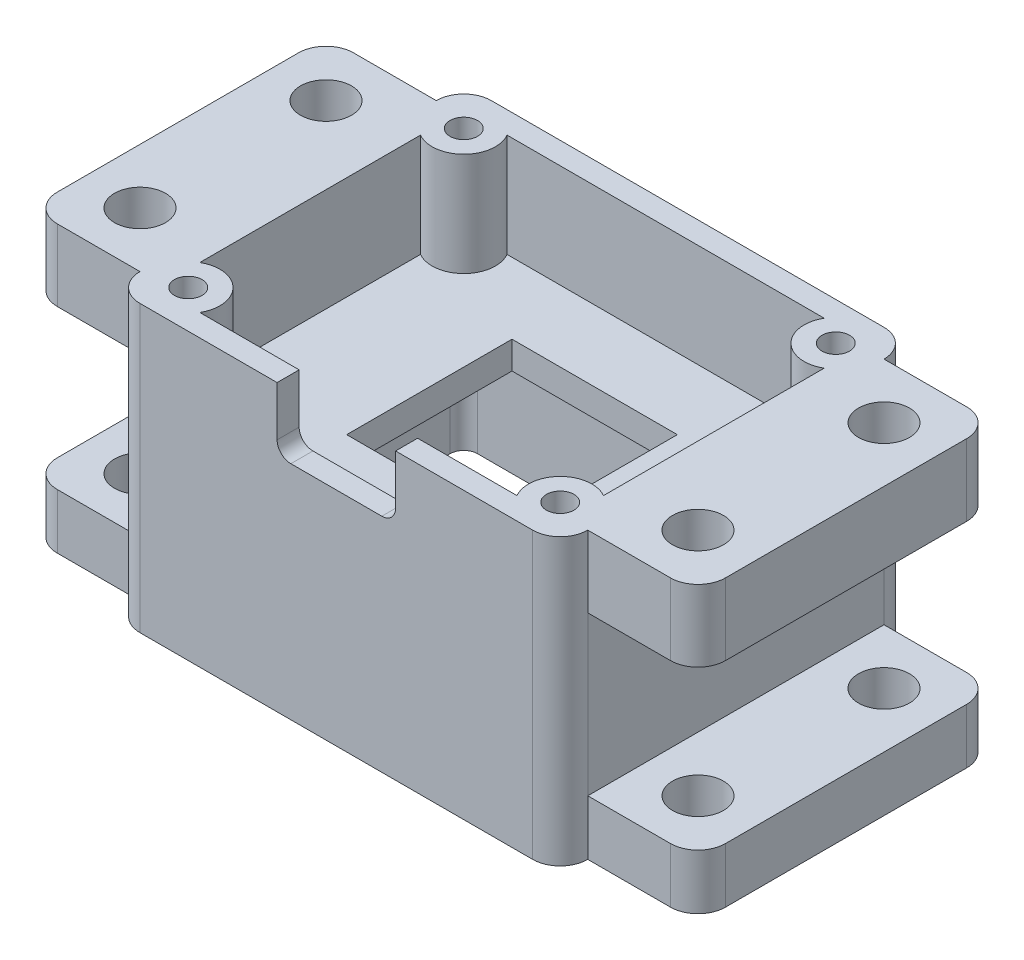
SolidWorks part; units mm, degrees
material "ABS"
ref_plane "Front" through (0, 0, 0) normal (0, 0, 1) x (1, 0, 0)
ref_plane "Top" through (0, 0, 0) normal (0, 1, 0) x (1, 0, 0)
ref_plane "Right" through (0, 0, 0) normal (1, 0, 0) x (0, 0, -1)
sketch "草图1" plane through (0, 0, 0) normal (0, 1, 0) x (1, 0, 0)
  line L0 (-14.25, 10.75) -> (-16.25, 10.75) construction
  line L5 (-14.25, 10.75) -> (14.25, 10.75)
  line L6 (-14.25, 10.75) -> (-14.25, -10.75)
  line L11 (-14.25, -10.75) -> (14.25, -10.75)
  line L12 (14.25, 10.75) -> (14.25, -10.75)
  line L13 (-14.25, 10.75) -> (14.25, -10.75) construction
  line L14 (-14.25, -10.75) -> (14.25, 10.75) construction
  line L15 (-16.25, 12.75) -> (16.25, 12.75)
  line L16 (-16.25, 12.75) -> (-16.25, -12.75)
  line L17 (-16.25, -12.75) -> (16.25, -12.75)
  line L18 (16.25, 12.75) -> (16.25, -12.75)
  line L19 (-16.25, 12.75) -> (16.25, -12.75) construction
  line L20 (-16.25, -12.75) -> (16.25, 12.75) construction
  line L21 (-14.25, 10.75) -> (-14.25, 12.75) construction
  point P0 (0, 0)
  point P6 (0, 0)
  dimension "D3" = 28.5
  dimension "D2" = 2
  dimension "D4" = 21.5
extrude "凸台-拉伸1" add sketch "草图1" along normal blind 13.2
sketch "草图2" plane through (0, 13.2, 0) normal (0, 1, 0) x (1, 0, 0)
  line L1 (-14.25, 10.75) -> (14.25, 10.75)
  line L2 (-14.25, 10.75) -> (-14.25, -10.75)
  line L3 (-14.25, -10.75) -> (14.25, -10.75)
  line L4 (14.25, 10.75) -> (14.25, -10.75)
  line L5 (-14.25, 10.75) -> (14.25, -10.75) construction
  line L6 (-14.25, -10.75) -> (14.25, 10.75) construction
  line L7 (-6, 6) -> (6, 6)
  line L8 (-6, 6) -> (-6, -6)
  line L9 (-6, -6) -> (6, -6)
  line L10 (6, 6) -> (6, -6)
  line L11 (-6, 6) -> (6, -6) construction
  line L12 (-6, -6) -> (6, 6) construction
  point P0 (0, 0)
  point P7 (0, 0)
  point P8 (0, 0)
  dimension "D1" = 12
extrude "凸台-拉伸2" add sketch "草图2" against normal blind 2
sketch "草图3" plane through (0, 13.2, 0) normal (0, 1, 0) x (1, 0, 0)
  line L0 (0, 0) -> (-16.25, 0) construction
  line L1 (-16.25, 12.75) -> (-16.25, -12.75) construction
  line L2 (-16.25, -12.75) -> (-16.25, 12.75)
  line L3 (-16.25, 12.75) -> (16.25, 12.75)
  line L4 (16.25, 12.75) -> (16.25, -0.0404)
  line L5 (16.25, -12.75) -> (16.25, 12.75) construction
  line L7 (14.25, 0.0137) -> (14.25, 10.75)
  line L8 (14.25, 10.75) -> (-14.25, 10.75)
  line L9 (-14.25, 10.75) -> (-14.25, -10.75)
  line L10 (14.25, -10.75) -> (-14.25, -10.75)
  line L11 (14.25, 0.0137) -> (14.25, -10.75)
  line L13 (16.25, -12.75) -> (16.25, -0.0404)
  line L14 (-16.25, -12.75) -> (16.25, -12.75)
  line L15 (14.25, 10.75) -> (-14.25, 10.75) construction
  line L16 (-14.25, 10.75) -> (-14.25, -10.75) construction
  line L17 (14.25, -10.75) -> (14.25, 10.75) construction
  point P17 (-14.25, 0)
extrude "凸台-拉伸3" add sketch "草图3" along normal blind 6.3
sketch "草图6" plane through (0, 19.5, 0) normal (0, 1, 0) x (1, 0, 0)
  line L0 (16.25, 0) -> (0, 0) construction
  line L2 (0, 0) -> (0, 12.75) construction
  line L4 (16.25, -12.75) -> (16.25, 12.75) construction
  line L5 (16.25, 12.75) -> (-16.25, 12.75) construction
  circle A0 centre (13.5, 10) radius 2.7
  circle A1 centre (13.5, -10) radius 2.7
  circle A2 centre (-13.5, -10) radius 2.7
  circle A3 centre (-13.5, 10) radius 2.7
  dimension "D1" = 5.4
  dimension "D2" = 27
  dimension "D3" = 20
extrude "凸台-拉伸4" add sketch "草图6" against normal up to next
sketch "草图7" plane through (0, 19.5, 0) normal (0, 1, 0) x (1, 0, 0)
  line L0 (0, 12.75) -> (0, 0) construction
  line L2 (0, 0) -> (16.25, 0) construction
  line L4 (16.25, 12.75) -> (-16.25, 12.75) construction
  line L5 (16.25, -12.75) -> (16.25, 12.75) construction
  circle A0 centre (13.5, 10) radius 1
  circle A1 centre (13.5, -10) radius 1
  circle A2 centre (-13.5, -10) radius 1
  circle A3 centre (-13.5, 10) radius 1
  dimension "D1" = 2
extrude "切除-拉伸3" cut sketch "草图7" against normal blind 5.5
sketch "草图10" plane through (0, 11.2, 0) normal (0, -1, 0) x (1, 0, 0)
  line L1 (-7.1, 7.1) -> (7.1, 7.1)
  line L2 (-7.1, 7.1) -> (-7.1, -7.1)
  line L3 (-7.1, -7.1) -> (7.1, -7.1)
  line L4 (7.1, 7.1) -> (7.1, -7.1)
  line L5 (-7.1, 7.1) -> (7.1, -7.1) construction
  line L6 (-7.1, -7.1) -> (7.1, 7.1) construction
  line L7 (-7.9, 7.9) -> (7.9, 7.9)
  line L8 (-7.9, 7.9) -> (-7.9, -7.9)
  line L9 (-7.9, -7.9) -> (7.9, -7.9)
  line L10 (7.9, 7.9) -> (7.9, -7.9)
  line L11 (-7.9, 7.9) -> (7.9, -7.9) construction
  line L12 (-7.9, -7.9) -> (7.9, 7.9) construction
  point P11 (0, 0)
  point P13 (0, 0)
  dimension "D1" = 14.2
  dimension "D2" = 0.8
extrude "凸台-拉伸5" add sketch "草图10" along normal blind 0.8 contours L10 L7 L8 L9 L1 L4 L3 L2 region at (0, 11.2, 7.6766)
sketch "草图11" plane through (0, 0, 12.75) normal (0, 0, 1) x (1, 0, 0)
  line L0 (0, 0) -> (0, 19.5) construction
  line L1 (-4, 17.65) -> (4, 17.65)
  line L2 (4, 17.65) -> (4, 15.8)
  line L3 (4, 15.8) -> (3, 14.8)
  line L4 (3, 14.8) -> (-3, 14.8)
  line L5 (-4, 15.8) -> (-3, 14.8)
  line L6 (-4, 17.65) -> (-4, 15.8)
  line L7 (-16.25, 19.5) -> (16.25, 19.5) construction
  line L8 (-10.9063, 13.2) -> (10.9063, 13.2) construction
  point P7 (0, 14.8)
  point P9 (0, 17.65)
  dimension "D1" = 8
  dimension "D2" = 135
  dimension "D3" = 1
  dimension "D4" = 1.6
  dimension "D5" = 2.85
extrude "切除-拉伸5" cut sketch "草图11" against normal blind 3
fillet "圆角6" radius 0.5 6 edges at (4, 15.8, 11.75) (3, 14.8, 11.75) (-3, 14.8, 11.75) (-4, 15.8, 11.75) (-4, 17.65, 11.75) (4, 17.65, 11.75)
fillet "圆角1" radius 2 4 edges at (16.25, 9.75, -12.75) (-16.25, 9.75, 12.75) (16.25, 9.75, 12.75) (-16.25, 9.75, -12.75)
fillet "圆角2" radius 1 4 edges at (14.25, 5.6, -10.75) (-14.25, 5.6, -10.75) (-14.25, 5.6, 10.75) (14.25, 5.6, 10.75)
sketch "草图12" plane through (16.25, 0, 0) normal (1, 0, 0) x (0, 0, -1)
  line L0 (-10.75, 0) -> (-10.75, 5)
  line L1 (-10.75, 19.5) -> (-10.75, 0) construction
  line L2 (-10.75, 5) -> (10.75, 5)
  line L3 (10.75, 0) -> (10.75, 19.5) construction
  line L4 (10.75, 5) -> (10.75, 0)
  line L5 (10.75, 0) -> (-10.75, 0)
extrude "凸台-拉伸7" add sketch "草图12" along normal blind 8
sketch "草图13" plane through (0, 5, 0) normal (0, 1, 0) x (1, 0, 0)
  circle A0 centre (20.25, 6.75) radius 1.85
  circle A1 centre (20.25, -6.75) radius 1.85
extrude "切除-拉伸7" cut sketch "草图13" against normal blind 8
fillet "圆角7" radius 2 2 edges at (24.25, 2.5, 10.75) (24.25, 2.5, -10.75)
sketch "草图15" plane through (16.25, 0, 0) normal (1, 0, 0) x (0, 0, -1)
  line L1 (-10.75, 19.5) -> (-10.75, 14.5)
  line L2 (-10.75, 19.5) -> (-10.75, 5) construction
  line L3 (-10.75, 14.5) -> (10.75, 14.5)
  line L4 (10.75, 5) -> (10.75, 19.5) construction
  line L5 (10.75, 14.5) -> (10.75, 19.5)
  line L6 (10.75, 19.5) -> (-10.75, 19.5)
extrude "凸台-拉伸8" add sketch "草图15" along normal blind 8
extrude "切除-拉伸8" cut sketch "草图13<3>" along normal blind 26
sketch "草图13<3>" plane through (0, 5, 0) normal (0, 1, 0) x (1, 0, 0) same geometry as "草图13"
fillet "圆角8" radius 2 2 edges at (24.25, 17, 10.75) (24.25, 17, -10.75)
ref_plane "基准面1" through (0, 0, 0) normal (1, 0, 0) x (0, 0, -1)
mirror "镜向1" about plane through (0, 0, 0) normal (1, 0, 0) of "切除-拉伸7", "凸台-拉伸7", "圆角7", "凸台-拉伸8", "切除-拉伸8", "圆角8"
other "移动面2" flip direction yes face at (0, 16.35, -10.75) face at (12.0845, 16.35, -8.5845) face at (-12.0845, 16.35, -8.5845) face at (-14.25, 16.35, 0) face at (-12.0845, 16.35, 8.5845) face at (14.25, 16.35, 0) face at (0, 16.0435, 10.75) face at (12.0845, 16.35, 8.5845) offset 0.4 parameters "D1"=0.4
other "移动面3" flip direction yes face at (2.977, 14.8556, 11.95) face at (3.5, 15.3, 11.95) face at (3.9444, 15.823, 11.95) face at (3.8018, 17.4518, 11.95) face at (4, 16.5786, 11.95) face at (0, 17.65, 11.95) face at (-3.8018, 17.4518, 11.95) face at (-4, 16.5786, 11.95) face at (-3.9444, 15.823, 11.95) face at (-3.5, 15.3, 11.95) face at (-2.977, 14.8556, 11.95) face at (0, 14.8, 11.95) offset 0.3 parameters "D1"=0.3
sketch "草图17" plane through (0, 5, 0) normal (0, 1, 0) x (1, 0, 0)
  line L4 (16.25, -10.75) -> (22.25, -10.75)
  line L5 (24.25, -8.75) -> (24.25, 8.75)
  line L6 (22.25, 10.75) -> (16.25, 10.75)
  line L7 (16.25, 10.75) -> (16.25, -10.75)
  line L8 (16.25, -10.75) -> (22.25, -10.75)
  line L9 (24.25, -8.75) -> (24.25, 8.75)
  line L10 (22.25, 10.75) -> (16.25, 10.75)
  line L11 (16.25, 10.75) -> (16.25, -10.75)
  arc A2 (22.25, -10.75) -> (24.25, -8.75) centre (22.25, -8.75) ccw
  arc A3 (24.25, 8.75) -> (22.25, 10.75) centre (22.25, 8.75) ccw
  arc A4 (22.25, -10.75) -> (24.25, -8.75) centre (22.25, -8.75) ccw
  arc A5 (24.25, 8.75) -> (22.25, 10.75) centre (22.25, 8.75) ccw
  dimension "D1" = 0
extrude "切除-拉伸9" cut sketch "草图17" against normal blind 1
sketch "草图18" plane through (0, 14.5, 0) normal (0, -1, 0) x (1, 0, 0)
  line L4 (24.25, -8.75) -> (24.25, 8.75)
  line L5 (22.25, 10.75) -> (16.25, 10.75)
  line L6 (16.25, 10.75) -> (16.25, -10.75)
  line L7 (16.25, -10.75) -> (22.25, -10.75)
  line L8 (24.25, -8.75) -> (24.25, 8.75)
  line L9 (22.25, 10.75) -> (16.25, 10.75)
  line L10 (16.25, 10.75) -> (16.25, -10.75)
  line L11 (16.25, -10.75) -> (22.25, -10.75)
  arc A2 (24.25, 8.75) -> (22.25, 10.75) centre (22.25, 8.75) ccw
  arc A3 (22.25, -10.75) -> (24.25, -8.75) centre (22.25, -8.75) ccw
  arc A4 (24.25, 8.75) -> (22.25, 10.75) centre (22.25, 8.75) ccw
  arc A5 (22.25, -10.75) -> (24.25, -8.75) centre (22.25, -8.75) ccw
  dimension "D1" = 0
extrude "切除-拉伸10" cut sketch "草图18" against normal blind 1
sketch "草图19" plane through (0, 14.5, 0) normal (0, -1, 0) x (1, 0, 0)
  line L4 (-16.25, 10.75) -> (-22.25, 10.75)
  line L5 (-24.25, 8.75) -> (-24.25, -8.75)
  line L6 (-22.25, -10.75) -> (-16.25, -10.75)
  line L7 (-16.25, -10.75) -> (-16.25, 10.75)
  line L8 (-16.25, 10.75) -> (-22.25, 10.75)
  line L9 (-24.25, 8.75) -> (-24.25, -8.75)
  line L10 (-22.25, -10.75) -> (-16.25, -10.75)
  line L11 (-16.25, -10.75) -> (-16.25, 10.75)
  arc A2 (-22.25, 10.75) -> (-24.25, 8.75) centre (-22.25, 8.75) ccw
  arc A3 (-24.25, -8.75) -> (-22.25, -10.75) centre (-22.25, -8.75) ccw
  arc A4 (-22.25, 10.75) -> (-24.25, 8.75) centre (-22.25, 8.75) ccw
  arc A5 (-24.25, -8.75) -> (-22.25, -10.75) centre (-22.25, -8.75) ccw
  dimension "D1" = 0
extrude "切除-拉伸11" cut sketch "草图19" against normal blind 1
sketch "草图20" plane through (0, 5, 0) normal (0, 1, 0) x (1, 0, 0)
  line L4 (-24.25, 8.75) -> (-24.25, -8.75)
  line L5 (-22.25, -10.75) -> (-16.25, -10.75)
  line L6 (-16.25, -10.75) -> (-16.25, 10.75)
  line L7 (-16.25, 10.75) -> (-22.25, 10.75)
  line L8 (-24.25, 8.75) -> (-24.25, -8.75)
  line L9 (-22.25, -10.75) -> (-16.25, -10.75)
  line L10 (-16.25, -10.75) -> (-16.25, 10.75)
  line L11 (-16.25, 10.75) -> (-22.25, 10.75)
  arc A2 (-24.25, -8.75) -> (-22.25, -10.75) centre (-22.25, -8.75) ccw
  arc A3 (-22.25, 10.75) -> (-24.25, 8.75) centre (-22.25, 8.75) ccw
  arc A4 (-24.25, -8.75) -> (-22.25, -10.75) centre (-22.25, -8.75) ccw
  arc A5 (-22.25, 10.75) -> (-24.25, 8.75) centre (-22.25, 8.75) ccw
  dimension "D1" = 0
extrude "切除-拉伸12" cut sketch "草图20" against normal blind 1
sketch "草图23" plane through (0, 19.5, 0) normal (0, 1, 0) x (1, 0, 0)
  line L0 (14.65, -8.0081) -> (14.65, 8.0081) construction
  line L1 (-11.5081, -11.15) -> (11.5081, -11.15) construction
  line L2 (-14.65, 8.0081) -> (-14.65, -8.0081) construction
  line L3 (11.5081, 11.15) -> (-11.5081, 11.15) construction
  line L4 (14.65, -8.0081) -> (14.65, 8.0081)
  line L5 (-11.5081, -11.15) -> (11.5081, -11.15)
  line L6 (-14.65, 8.0081) -> (-14.65, -8.0081)
  line L7 (11.5081, 11.15) -> (-11.5081, 11.15)
  line L8 (-24.25, 8.75) -> (-24.25, -8.75)
  line L9 (-22.25, -10.75) -> (-16.25, -10.75)
  line L10 (-14.25, -12.75) -> (14.25, -12.75)
  line L11 (16.25, -10.75) -> (22.25, -10.75)
  line L12 (24.25, -8.75) -> (24.25, 8.75)
  line L13 (22.25, 10.75) -> (16.25, 10.75)
  line L14 (14.25, 12.75) -> (-14.25, 12.75)
  line L15 (-16.25, 10.75) -> (-22.25, 10.75)
  line L16 (-24.25, 8.75) -> (-24.25, -8.75)
  line L17 (-22.25, -10.75) -> (-16.25, -10.75)
  line L18 (-14.25, -12.75) -> (14.25, -12.75)
  line L19 (16.25, -10.75) -> (22.25, -10.75)
  line L20 (24.25, -8.75) -> (24.25, 8.75)
  line L21 (22.25, 10.75) -> (16.25, 10.75)
  line L22 (14.25, 12.75) -> (-14.25, 12.75)
  line L23 (-16.25, 10.75) -> (-22.25, 10.75)
  arc A0 (11.5081, 11.15) -> (14.65, 8.0081) centre (13.5, 10) ccw construction
  arc A1 (14.65, -8.0081) -> (11.5081, -11.15) centre (13.5, -10) ccw construction
  arc A2 (-11.5081, -11.15) -> (-14.65, -8.0081) centre (-13.5, -10) ccw construction
  arc A3 (-14.65, 8.0081) -> (-11.5081, 11.15) centre (-13.5, 10) ccw construction
  arc A4 (11.5081, 11.15) -> (14.65, 8.0081) centre (13.5, 10) ccw
  arc A5 (14.65, -8.0081) -> (11.5081, -11.15) centre (13.5, -10) ccw
  arc A6 (-11.5081, -11.15) -> (-14.65, -8.0081) centre (-13.5, -10) ccw
  arc A7 (-14.65, 8.0081) -> (-11.5081, 11.15) centre (-13.5, 10) ccw
  arc A8 (-24.25, -8.75) -> (-22.25, -10.75) centre (-22.25, -8.75) ccw
  arc A9 (-16.25, -10.75) -> (-14.25, -12.75) centre (-14.25, -10.75) ccw
  arc A10 (14.25, -12.75) -> (16.25, -10.75) centre (14.25, -10.75) ccw
  arc A11 (22.25, -10.75) -> (24.25, -8.75) centre (22.25, -8.75) ccw
  arc A12 (24.25, 8.75) -> (22.25, 10.75) centre (22.25, 8.75) ccw
  arc A13 (16.25, 10.75) -> (14.25, 12.75) centre (14.25, 10.75) ccw
  arc A14 (-14.25, 12.75) -> (-16.25, 10.75) centre (-14.25, 10.75) ccw
  arc A15 (-22.25, 10.75) -> (-24.25, 8.75) centre (-22.25, 8.75) ccw
  arc A16 (-24.25, -8.75) -> (-22.25, -10.75) centre (-22.25, -8.75) ccw
  arc A17 (-16.25, -10.75) -> (-14.25, -12.75) centre (-14.25, -10.75) ccw
  arc A18 (14.25, -12.75) -> (16.25, -10.75) centre (14.25, -10.75) ccw
  arc A19 (22.25, -10.75) -> (24.25, -8.75) centre (22.25, -8.75) ccw
  arc A20 (24.25, 8.75) -> (22.25, 10.75) centre (22.25, 8.75) ccw
  arc A21 (16.25, 10.75) -> (14.25, 12.75) centre (14.25, 10.75) ccw
  arc A22 (-14.25, 12.75) -> (-16.25, 10.75) centre (-14.25, 10.75) ccw
  arc A23 (-22.25, 10.75) -> (-24.25, 8.75) centre (-22.25, 8.75) ccw
  circle A24 centre (20.25, -6.75) radius 1.85 construction
  circle A25 centre (20.25, 6.75) radius 1.85 construction
  circle A26 centre (-20.25, -6.75) radius 1.85 construction
  circle A27 centre (-20.25, 6.75) radius 1.85 construction
  circle A28 centre (20.25, -6.75) radius 1.85
  circle A29 centre (20.25, 6.75) radius 1.85
  circle A30 centre (-20.25, -6.75) radius 1.85
  circle A31 centre (-20.25, 6.75) radius 1.85
  circle A32 centre (13.5, -10) radius 1 construction
  circle A33 centre (13.5, 10) radius 1 construction
  circle A34 centre (-13.5, -10) radius 1 construction
  circle A35 centre (-13.5, 10) radius 1 construction
  circle A36 centre (13.5, -10) radius 1
  circle A37 centre (13.5, 10) radius 1
  circle A38 centre (-13.5, -10) radius 1
  circle A39 centre (-13.5, 10) radius 1
  dimension "D1" = 0
extrude "凸台-拉伸9" add sketch "草图23" along normal blind 1.2
sketch "草图25" plane through (-4.3, 0, 0) normal (1, 0, 0) x (0, 0, -1)
  line L0 (-12.75, 16.0175) -> (-12.75, 20.7)
  line L1 (-12.75, 0) -> (-12.75, 20.7) construction
  line L2 (-12.75, 20.7) -> (-10.75, 20.7)
  line L3 (-10.75, 20.7) -> (-10.75, 16.0175)
  line L4 (-10.75, 15.5) -> (-10.75, 20.7) construction
  line L5 (-10.75, 16.0175) -> (-12.75, 16.0175)
extrude "切除-拉伸13" cut sketch "草图25" along normal blind 8.6
sketch "草图26" plane through (0, 14.5, 0) normal (0, 1, 0) x (1, 0, 0)
  line L0 (2.7929, -12.75) -> (4.3, -12.75)
  line L1 (-2.7929, -12.75) -> (-4.3, -12.75)
  line L2 (-4.3, -12.75) -> (-4.3, -11.15)
  line L3 (-4.3, -11.15) -> (-2.7929, -11.15)
  line L4 (-2.7929, -12.75) -> (2.7929, -12.75)
  line L5 (2.7929, -12.75) -> (2.7929, -11.15)
  line L6 (2.7929, -11.15) -> (-2.7929, -11.15)
  line L7 (-2.7929, -11.15) -> (-2.7929, -12.75)
  line L8 (-2.7929, -12.75) -> (2.7929, -12.75)
  line L10 (2.7929, -11.15) -> (-2.7929, -11.15)
  line L12 (4.0657, -12.75) -> (4.3, -12.75) construction
  line L13 (4.3, -12.75) -> (4.3, -11.15)
  line L14 (4.3, -11.15) -> (2.7929, -11.15)
  dimension "D1" = 0
extrude "凸台-拉伸11" add sketch "草图26" along normal blind 1.6
fillet "圆角9" radius 1 2 edges at (4.3, 16.1, 11.95)
